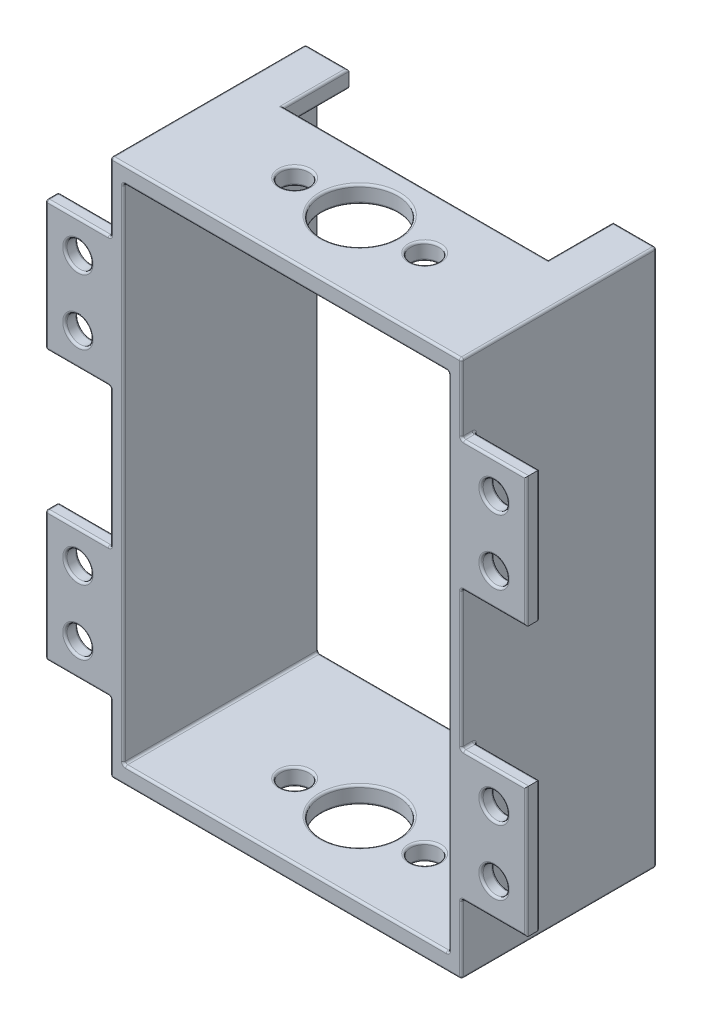
SolidWorks part; units mm, degrees
ref_plane "Front Plane" through (0, 0, 0) normal (0, 0, 1) x (1, 0, 0)
ref_plane "Top Plane" through (0, 0, 0) normal (0, 1, 0) x (1, 0, 0)
ref_plane "Right Plane" through (0, 0, 0) normal (1, 0, 0) x (0, 0, -1)
sketch "Sketch1" plane through (0, 0, 0) normal (0, 1, 0) x (1, 0, 0)
  line L0 (37.5, 45) -> (37.5, 0) construction
  line L1 (0, 0) -> (75, 0)
  line L2 (0, 0) -> (0, 45)
  line L3 (0, 45) -> (75, 45)
  line L4 (75, 0) -> (75, 45)
  line L5 (0, 17) -> (37.5, 17) construction
  line L6 (37.5, 17) -> (75, 17) construction
  circle A2 centre (37.5, 17) radius 8.75
  circle A5 centre (22.5, 17) radius 3.25
  circle A6 centre (52.5, 17) radius 3.25
  dimension "D2" = 6.5
  dimension "D3" = 17.5
  dimension "D1" = 45
  dimension "D4" = 75
  dimension "D5" = 15
  dimension "D6" = 17
extrude "Boss-Extrude1" add sketch "Sketch1" along normal blind 4
sketch "Sketch2" plane through (0, 0, 0) normal (-1, 0, 0) x (0, 0, 1)
  line L0 (-45, 4) -> (-45, 0) construction
  line L1 (0, 0) -> (-45, 0)
  line L2 (0, 0) -> (0, 120)
  line L3 (0, 120) -> (-45, 120)
  line L4 (-45, 0) -> (-45, 120)
  dimension "D1" = 120
extrude "Boss-Extrude2" add sketch "Sketch2" along normal blind 3
ref_plane "Plane1" through (37.5, 0, 0) normal (1, 0, 0) x (0, 0, -1)
mirror "Mirror1" about plane through (37.5, 0, 0) normal (1, 0, 0) of "Boss-Extrude2"
sketch "Sketch3" plane through (0, 120, 0) normal (0, 1, 0) x (1, 0, 0)
  line L1 (-3, 0) -> (78, 0)
  line L2 (-3, 0) -> (-3, 45)
  line L3 (-3, 45) -> (78, 45)
  line L4 (78, 0) -> (78, 45)
  circle A1 centre (37.5, 17) radius 8.75
  circle A2 centre (22.5, 17) radius 3.25
  circle A3 centre (22.5, 17) radius 3.25 construction
  circle A4 centre (52.5, 17) radius 3.25
  circle A5 centre (52.5, 17) radius 3.25 construction
  circle A6 centre (37.5, 17) radius 8.75 construction
extrude "Boss-Extrude3" add sketch "Sketch3" along normal blind 4
sketch "Sketch5" plane through (0, 0, 0) normal (0, 0, 1) x (1, 0, 0)
  line L0 (78, 62) -> (-3, 62) construction
  line L1 (78, 0) -> (78, 124) construction
  line L2 (-3, 0) -> (-3, 124) construction
  line L3 (78, 124) -> (-3, 62) construction
  line L4 (-3, 78) -> (-18, 78)
  line L5 (-3, 78) -> (-3, 108)
  line L6 (-3, 108) -> (-18, 108)
  line L7 (-18, 78) -> (-18, 108)
  line L8 (-3, 108) -> (-18, 93) construction
  line L9 (-18, 93) -> (-3, 93) construction
  line L10 (-3, 16) -> (-18, 16)
  line L11 (-18, 46) -> (-18, 16)
  line L12 (-3, 46) -> (-18, 46)
  line L13 (-3, 46) -> (-3, 16)
  circle A0 centre (-10.5, 100.5) radius 3
  circle A1 centre (-10.5, 85.5) radius 3
  circle A2 centre (-10.5, 38.5) radius 3
  circle A3 centre (-10.5, 23.5) radius 3
  point P11 (37.5, 93)
  point P13 (-3, 93)
  dimension "D3" = 6
  dimension "D1" = 15
  dimension "D2" = 30
extrude "Boss-Extrude5" add sketch "Sketch5" against normal blind 3
mirror "Mirror2" about plane through (37.5, 0, 0) normal (1, 0, 0) of "Boss-Extrude5"
sketch "Sketch6" plane through (0, 124, 0) normal (0, 1, 0) x (1, 0, 0)
  line L0 (37.5, 45) -> (37.5, 0) construction
  line L1 (78, 45) -> (-3, 45) construction
  line L2 (-3, 0) -> (78, 0) construction
  line L4 (7, 45) -> (68, 45)
  line L5 (7, 45) -> (7, 30)
  line L6 (7, 30) -> (68, 30)
  line L7 (68, 45) -> (68, 30)
  line L11 (-3, 45) -> (-3, 0) construction
  point P10 (37.5, 45)
  dimension "D1" = 10
  dimension "D2" = 15
extrude "Cut-Extrude1" cut sketch "Sketch6" against normal up to next
fillet "Fillet1" radius 0.5 104 edges at (71.5, 120, -45) (3.5, 120, -45) (37.5, 4, -45) (-3, 62, -45) (-3, 108, -1.5) (-3, 78, -1.5) (-3, 46, -1.5) (-3, 16, -1.5) (75, 62, -45) (75, 120, -22.5) (75, 4, -22.5) (0, 120, -22.5) (0, 62, -45) (0, 4, -22.5) (52.5, 124, -13.75) (22.5, 124, -13.75) (37.5, 124, -8.25) (-3, 124, -22.5) (2, 124, -45) (7, 124, -37.5) (37.5, 124, -30) (68, 124, -37.5) (73, 124, -45) (88.5, 23.5, 0) (82.5, 38.5, 0) (88.5, 85.5, 0) (82.5, 100.5, 0) (-7.5, 38.5, 0) (-13.5, 23.5, 0) (-7.5, 100.5, 0) (-13.5, 85.5, 0) (-3, 8, 0) (-10.5, 16, 0) (-10.5, 46, 0) (-3, 62, 0) (-10.5, 78, 0) (-10.5, 108, 0) (-3, 116, 0) (37.5, 124, 0) (85.5, 108, 0) (93, 93, 0) (85.5, 78, 0) (85.5, 46, 0) (93, 31, 0) (85.5, 16, 0) (37.5, 4, 0) (75, 62, 0) (37.5, 120, 0) (0, 62, 0) (88.5, 23.5, -3) (85.5, 16, -3) (93, 31, -3) (85.5, 46, -3) (82.5, 38.5, -3) (88.5, 85.5, -3) (82.5, 100.5, -3) (85.5, 78, -3) (93, 93, -3) (85.5, 108, -3) (78, 78, -1.5) (78, 93, -3) (78, 108, -1.5) (78, 116, 0) (78, 124, -22.5) (78, 62, -45) (78, 8, 0) (78, 16, -1.5) (78, 31, -3) (78, 46, -1.5) (78, 62, 0) (37.5, 0, -8.25) (22.5, 0, -13.75) (78, 0, -22.5) (37.5, 0, -45) (-3, 0, -22.5) (37.5, 0, 0) (52.5, 0, -20.25) (-10.5, 108, -3) (-10.5, 78, -3) (-3, 93, -3) (-7.5, 100.5, -3) (-13.5, 85.5, -3) (-10.5, 46, -3) (-10.5, 16, -3) (-3, 31, -3) (-7.5, 38.5, -3) (-13.5, 23.5, -3) (-18, 78, -1.5) (-18, 93, -3) (-18, 108, -1.5) (-18, 93, 0) (-18, 16, -1.5) (-18, 31, -3) (-18, 46, -1.5) (-18, 31, 0) (52.5, 120, -13.75) (37.5, 120, -8.25) (22.5, 120, -13.75) (37.5, 120, -30) (7, 120, -37.5) (68, 120, -37.5) (37.5, 4, -8.25) (52.5, 4, -20.25) (22.5, 4, -13.75)
equation "\"length\"=120"
equation "\"D1@Sketch2\"=\"length\""
equation "\"D3@LPattern1\"=\"length\""
